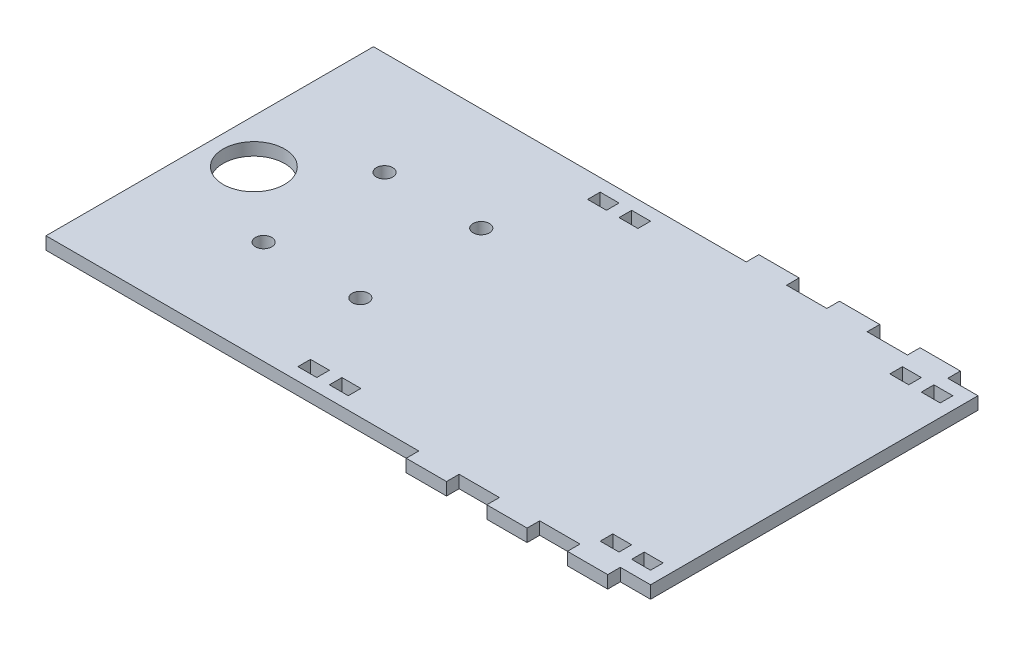
SolidWorks part; units mm, degrees
ref_plane "Front Plane" through (0, 0, 0) normal (0, 0, 1) x (1, 0, 0)
ref_plane "Top Plane" through (0, 0, 0) normal (0, 1, 0) x (1, 0, 0)
ref_plane "Right Plane" through (0, 0, 0) normal (1, 0, 0) x (0, 0, -1)
sketch "Sketch1" plane through (0, 0, 0) normal (0, 1, 0) x (1, 0, 0)
  line L0 (38.1, -41.275) -> (48.26, -41.275)
  line L1 (76.2, -41.275) -> (-76.2, -41.275)
  line L2 (76.2, -41.275) -> (76.2, 41.275)
  line L3 (76.2, 41.275) -> (-76.2, 41.275)
  line L4 (-76.2, -41.275) -> (-76.2, 41.275)
  line L5 (76.2, -41.275) -> (-76.2, 41.275) construction
  line L6 (76.2, 41.275) -> (-76.2, -41.275) construction
  line L7 (58.42, -41.275) -> (68.58, -41.275)
  line L8 (58.42, -41.275) -> (58.42, -44.45)
  line L9 (58.42, -44.45) -> (68.58, -44.45)
  line L10 (68.58, -41.275) -> (68.58, -44.45)
  line L11 (38.1, -41.275) -> (38.1, -44.45)
  line L12 (38.1, -44.45) -> (48.26, -44.45)
  line L13 (48.26, -41.275) -> (48.26, -44.45)
  line L14 (17.78, -41.275) -> (27.94, -41.275)
  line L15 (17.78, -41.275) -> (17.78, -44.45)
  line L16 (17.78, -44.45) -> (27.94, -44.45)
  line L17 (27.94, -41.275) -> (27.94, -44.45)
  line L18 (58.42, 44.45) -> (68.58, 44.45)
  line L19 (58.42, 44.45) -> (58.42, 41.275)
  line L20 (58.42, 41.275) -> (68.58, 41.275)
  line L21 (68.58, 44.45) -> (68.58, 41.275)
  line L22 (38.1, 44.45) -> (48.26, 44.45)
  line L23 (38.1, 44.45) -> (38.1, 41.275)
  line L24 (38.1, 41.275) -> (48.26, 41.275)
  line L25 (48.26, 44.45) -> (48.26, 41.275)
  line L26 (17.78, 44.45) -> (27.94, 44.45)
  line L27 (17.78, 44.45) -> (17.78, 41.275)
  line L28 (17.78, 41.275) -> (27.94, 41.275)
  line L29 (27.94, 44.45) -> (27.94, 41.275)
  line L30 (58.42, -41.275) -> (38.1, -41.275) construction
  circle A0 centre (-65.0766, 0) radius 7.747
  point P0 (0, 0)
  dimension "D9" = 15.494
  dimension "D1" = 3.175
  dimension "D2" = 10.16
  dimension "D5" = 20.32
  dimension "D6" = 82.55
  dimension "D7" = 152.4
  dimension "D8" = 7.62
  dimension "D3" = 3
  dimension "D4" = 2
extrude "Boss-Extrude1" add sketch "Sketch1" along normal blind 3.175 contours L17 L1 L15 L16 | L4 L1 L0 L2 L3 | L13 L0 L11 L12 | L29 L26 L27 L3 | L10 L9 L8 L7 | L18 L21 L20 L19 | L22 L25 L24 L23 region at (0.9901, 0, 0) region at (43.18, 0, 42.8625) region at (22.86, 0, 42.8625) region at (22.86, 0, -42.8625)
sketch "Sketch2" plane through (0, 3.175, 0) normal (0, 1, 0) x (1, 0, 0)
  line L0 (-47.3754, 15.24) -> (-47.3754, -15.24) construction
  line L1 (-47.3754, 0) -> (-76.2, 0) construction
  line L2 (-76.2, -41.275) -> (-76.2, 41.275) construction
  circle A0 centre (-47.3754, 15.24) radius 2.0638
  circle A1 centre (-22.9914, 15.24) radius 2.0638
  circle A2 centre (-22.9914, -15.24) radius 2.0638
  circle A3 centre (-47.3754, -15.24) radius 2.0638
  dimension "D4" = 24.384
  dimension "D5" = 4.1275
  dimension "D3" = 30.48
  dimension "D1" = 2
  dimension "D2" = 2
extrude "Caster Mounting Holes" cut sketch "Sketch2" against normal through all
sketch "Sketch3" plane through (0, 3.175, 0) normal (0, 1, 0) x (1, 0, 0)
  line L0 (58.42, 41.275) -> (48.26, 41.275) construction
  line L2 (65.0875, 38.1) -> (65.0875, 34.925)
  line L4 (68.2625, 38.1) -> (68.2625, 34.925)
  line L7 (76.2, -41.275) -> (76.2, 41.275) construction
  line L9 (68.2625, 38.1) -> (73.025, 38.1)
  line L10 (73.025, 38.1) -> (73.025, 34.925)
  line L11 (73.025, 34.925) -> (68.2625, 34.925)
  line L15 (65.0875, 34.925) -> (60.325, 34.925)
  line L16 (60.325, 34.925) -> (60.325, 38.1)
  line L17 (60.325, 38.1) -> (65.0875, 38.1)
  point P0 (66.675, 36.5125)
  dimension "D1" = 3.175
  dimension "D2" = 4.7625
  dimension "D3" = 3.175
  dimension "D4" = 3.175
  dimension "D5" = 3.175
extrude "Cut-Extrude1" cut sketch "Sketch3" against normal through all contours L17 L16 L15 L2 | L11 L10 L9 L4 region at (62.7063, 3.175, -36.5125) region at (70.6438, 3.175, -36.5125)
pattern_linear "LPattern1" count 2 spacing 76.2 along (-1, 0, 0) count 2 spacing 73.025 along (0, 0, 1) of "Cut-Extrude1"
sketch "Sketch4" plane through (0, 3.175, 0) normal (0, 1, 0) x (1, 0, 0)
  line L9 (-11.1887, -38.0238) -> (-11.1887, -35.0012)
  line L10 (-15.7988, -38.0238) -> (-11.1887, -38.0238)
  line L11 (-15.7988, -35.0012) -> (-15.7988, -38.0238)
  line L12 (-11.1887, -35.0012) -> (-15.7988, -35.0012)
  line L13 (-11.1887, -38.0238) -> (-11.1887, -35.0012)
  line L14 (-15.7988, -38.0238) -> (-11.1887, -38.0238)
  line L15 (-15.7988, -35.0012) -> (-15.7988, -38.0238)
  line L16 (-11.1887, -35.0012) -> (-15.7988, -35.0012)
  line L21 (-3.2512, -38.0238) -> (-3.2512, -35.0012)
  line L22 (-3.2512, -35.0012) -> (-7.8613, -35.0012)
  line L23 (-7.8613, -35.0012) -> (-7.8613, -38.0238)
  line L24 (-7.8613, -38.0238) -> (-3.2512, -38.0238)
  line L25 (-3.2512, -38.0238) -> (-3.2512, -35.0012)
  line L26 (-3.2512, -35.0012) -> (-7.8613, -35.0012)
  line L27 (-7.8613, -35.0012) -> (-7.8613, -38.0238)
  line L28 (-7.8613, -38.0238) -> (-3.2512, -38.0238)
  line L33 (60.4012, -38.0238) -> (65.0113, -38.0238)
  line L34 (60.4012, -35.0012) -> (60.4012, -38.0238)
  line L35 (65.0113, -35.0012) -> (60.4012, -35.0012)
  line L36 (65.0113, -38.0238) -> (65.0113, -35.0012)
  line L37 (60.4012, -38.0238) -> (65.0113, -38.0238)
  line L38 (60.4012, -35.0012) -> (60.4012, -38.0238)
  line L39 (65.0113, -35.0012) -> (60.4012, -35.0012)
  line L40 (65.0113, -38.0238) -> (65.0113, -35.0012)
  line L45 (72.9488, -35.0012) -> (68.3387, -35.0012)
  line L46 (68.3387, -35.0012) -> (68.3387, -38.0238)
  line L47 (72.9488, -38.0238) -> (72.9488, -35.0012)
  line L48 (68.3387, -38.0238) -> (72.9488, -38.0238)
  line L49 (72.9488, -35.0012) -> (68.3387, -35.0012)
  line L50 (68.3387, -35.0012) -> (68.3387, -38.0238)
  line L51 (72.9488, -38.0238) -> (72.9488, -35.0012)
  line L52 (68.3387, -38.0238) -> (72.9488, -38.0238)
  line L57 (65.0113, 35.0012) -> (65.0113, 38.0238)
  line L58 (65.0113, 38.0238) -> (60.4012, 38.0238)
  line L59 (60.4012, 38.0238) -> (60.4012, 35.0012)
  line L60 (60.4012, 35.0012) -> (65.0113, 35.0012)
  line L61 (65.0113, 35.0012) -> (65.0113, 38.0238)
  line L62 (65.0113, 38.0238) -> (60.4012, 38.0238)
  line L63 (60.4012, 38.0238) -> (60.4012, 35.0012)
  line L64 (60.4012, 35.0012) -> (65.0113, 35.0012)
  line L69 (72.9488, 35.0012) -> (72.9488, 38.0238)
  line L70 (72.9488, 38.0238) -> (68.3387, 38.0238)
  line L71 (68.3387, 38.0238) -> (68.3387, 35.0012)
  line L72 (68.3387, 35.0012) -> (72.9488, 35.0012)
  line L73 (72.9488, 35.0012) -> (72.9488, 38.0238)
  line L74 (72.9488, 38.0238) -> (68.3387, 38.0238)
  line L75 (68.3387, 38.0238) -> (68.3387, 35.0012)
  line L76 (68.3387, 35.0012) -> (72.9488, 35.0012)
  line L81 (-7.8613, 38.0238) -> (-7.8613, 35.0012)
  line L82 (-3.2512, 38.0238) -> (-7.8613, 38.0238)
  line L83 (-3.2512, 35.0012) -> (-3.2512, 38.0238)
  line L84 (-7.8613, 35.0012) -> (-3.2512, 35.0012)
  line L85 (-7.8613, 38.0238) -> (-7.8613, 35.0012)
  line L86 (-3.2512, 38.0238) -> (-7.8613, 38.0238)
  line L87 (-3.2512, 35.0012) -> (-3.2512, 38.0238)
  line L88 (-7.8613, 35.0012) -> (-3.2512, 35.0012)
  line L93 (-15.7988, 38.0238) -> (-15.7988, 35.0012)
  line L94 (-11.1887, 38.0238) -> (-15.7988, 38.0238)
  line L95 (-11.1887, 35.0012) -> (-11.1887, 38.0238)
  line L96 (-15.7988, 35.0012) -> (-11.1887, 35.0012)
  line L97 (-15.7988, 38.0238) -> (-15.7988, 35.0012)
  line L98 (-11.1887, 38.0238) -> (-15.7988, 38.0238)
  line L99 (-11.1887, 35.0012) -> (-11.1887, 38.0238)
  line L100 (-15.7988, 35.0012) -> (-11.1887, 35.0012)
  line L455 (17.7038, 44.5262) -> (17.7038, 41.3512)
  line L456 (28.0162, 44.5262) -> (17.7038, 44.5262)
  line L457 (28.0162, 41.3512) -> (28.0162, 44.5262)
  line L458 (38.0238, 41.3512) -> (28.0162, 41.3512)
  line L459 (38.0238, 44.5262) -> (38.0238, 41.3512)
  line L460 (48.3362, 44.5262) -> (38.0238, 44.5262)
  line L461 (48.3362, 41.3512) -> (48.3362, 44.5262)
  line L462 (58.3438, 41.3512) -> (48.3362, 41.3512)
  line L463 (58.3438, 44.5262) -> (58.3438, 41.3512)
  line L464 (68.6562, 44.5262) -> (58.3438, 44.5262)
  line L465 (68.6562, 41.3512) -> (68.6562, 44.5262)
  line L466 (76.2762, 41.3512) -> (68.6562, 41.3512)
  line L467 (68.6562, -41.3512) -> (76.2762, -41.3512)
  line L468 (68.6562, -44.5262) -> (68.6562, -41.3512)
  line L469 (58.3438, -44.5262) -> (68.6562, -44.5262)
  line L470 (58.3438, -41.3512) -> (58.3438, -44.5262)
  line L471 (48.3362, -41.3512) -> (58.3438, -41.3512)
  line L472 (48.3362, -44.5262) -> (48.3362, -41.3512)
  line L473 (38.0238, -44.5262) -> (48.3362, -44.5262)
  line L474 (38.0238, -41.3512) -> (38.0238, -44.5262)
  line L475 (28.0162, -41.3512) -> (38.0238, -41.3512)
  line L476 (28.0162, -44.5262) -> (28.0162, -41.3512)
  line L477 (17.7038, -44.5262) -> (28.0162, -44.5262)
  line L478 (17.7038, -41.3512) -> (17.7038, -44.5262)
  line L479 (76.2762, -41.3512) -> (76.2762, 41.3512)
  line L480 (-76.2762, -41.3512) -> (17.7038, -41.3512)
  line L481 (17.7038, 41.3512) -> (-76.2762, 41.3512)
  line L482 (-76.2762, 41.3512) -> (-76.2762, -41.3512)
  line L483 (17.7038, 44.5262) -> (17.7038, 41.3512)
  line L484 (28.0162, 44.5262) -> (17.7038, 44.5262)
  line L485 (28.0162, 41.3512) -> (28.0162, 44.5262)
  line L486 (38.0238, 41.3512) -> (28.0162, 41.3512)
  line L487 (38.0238, 44.5262) -> (38.0238, 41.3512)
  line L488 (48.3362, 44.5262) -> (38.0238, 44.5262)
  line L489 (48.3362, 41.3512) -> (48.3362, 44.5262)
  line L490 (58.3438, 41.3512) -> (48.3362, 41.3512)
  line L491 (58.3438, 44.5262) -> (58.3438, 41.3512)
  line L492 (68.6562, 44.5262) -> (58.3438, 44.5262)
  line L493 (68.6562, 41.3512) -> (68.6562, 44.5262)
  line L494 (76.2762, 41.3512) -> (68.6562, 41.3512)
  line L495 (68.6562, -41.3512) -> (76.2762, -41.3512)
  line L496 (68.6562, -44.5262) -> (68.6562, -41.3512)
  line L497 (58.3438, -44.5262) -> (68.6562, -44.5262)
  line L498 (58.3438, -41.3512) -> (58.3438, -44.5262)
  line L499 (48.3362, -41.3512) -> (58.3438, -41.3512)
  line L500 (48.3362, -44.5262) -> (48.3362, -41.3512)
  line L501 (38.0238, -44.5262) -> (48.3362, -44.5262)
  line L502 (38.0238, -41.3512) -> (38.0238, -44.5262)
  line L503 (28.0162, -41.3512) -> (38.0238, -41.3512)
  line L504 (28.0162, -44.5262) -> (28.0162, -41.3512)
  line L505 (17.7038, -44.5262) -> (28.0162, -44.5262)
  line L506 (17.7038, -41.3512) -> (17.7038, -44.5262)
  line L507 (76.2762, -41.3512) -> (76.2762, 41.3512)
  line L508 (-76.2762, -41.3512) -> (17.7038, -41.3512)
  line L509 (17.7038, 41.3512) -> (-76.2762, 41.3512)
  line L510 (-76.2762, 41.3512) -> (-76.2762, -41.3512)
  circle A2 centre (-47.3754, -15.24) radius 1.9876
  circle A3 centre (-47.3754, -15.24) radius 1.9876
  circle A4 centre (-65.0766, 0) radius 7.6708
  circle A5 centre (-47.3754, 15.24) radius 1.9876
  circle A6 centre (-47.3754, 15.24) radius 1.9876
  circle A7 centre (-65.0766, 0) radius 7.6708
  circle A8 centre (-22.9914, 15.24) radius 1.9876
  circle A9 centre (-22.9914, 15.24) radius 1.9876
  circle A11 centre (-22.9914, -15.24) radius 1.9876
  circle A12 centre (-22.9914, -15.24) radius 1.9876
  dimension "D1" = 0.0762
  dimension "D2" = 0.0762
  dimension "D3" = 0.0762
  dimension "D4" = 0.0762
  dimension "D5" = 0.0762
  dimension "D6" = 0.0762
  dimension "D7" = 0.0762
  dimension "D8" = 0.0762
  dimension "D9" = 0.0762
  dimension "D10" = 0.0762
  dimension "D11" = 0.0762
  dimension "D12" = 0.0762
  dimension "D13" = 0.0762
  dimension "D14" = 0.0762
